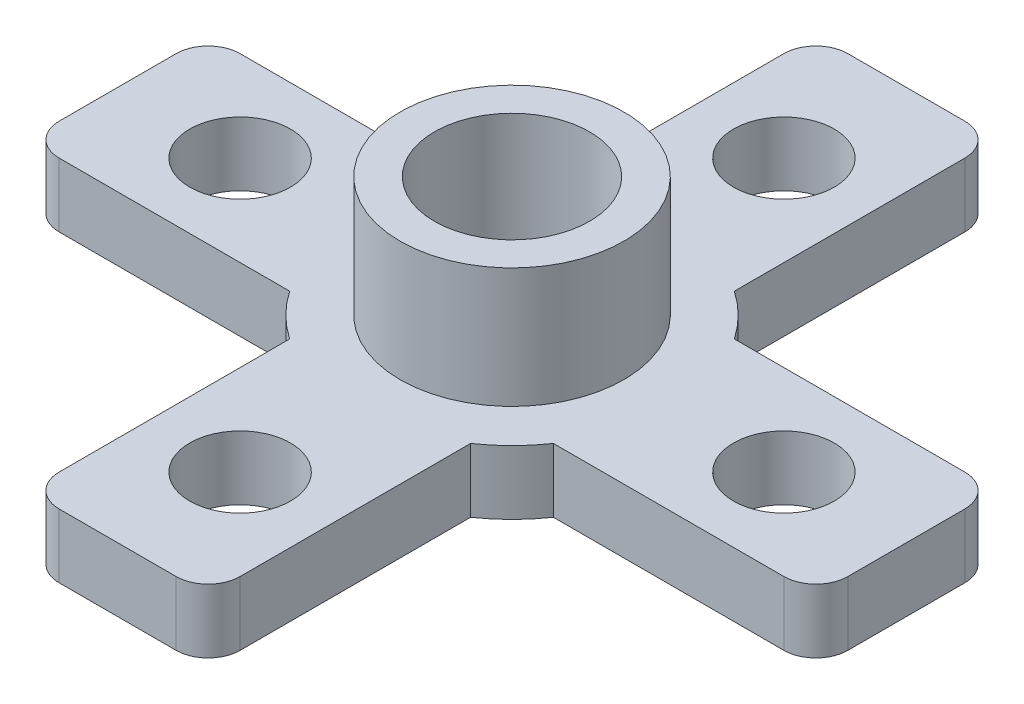
SolidWorks part; units mm, degrees
note: The reader was unsure of these and kept them because the rebuilt part matched: shared geometry of "Sketch1<3>", "Sketch1<4>".
ref_plane "Front Plane" through (0, 0, 0) normal (0, 0, 1) x (1, 0, 0)
ref_plane "Top Plane" through (0, 0, 0) normal (0, 1, 0) x (1, 0, 0)
ref_plane "Right Plane" through (0, 0, 0) normal (1, 0, 0) x (0, 0, -1)
sketch "Sketch1" plane through (0, 0, 0) normal (0, 1, 0) x (1, 0, 0)
  line L0 (2.8284, 2.8284) -> (12.3284, 2.8284)
  line L1 (-2.8284, 2.8284) -> (2.8284, -2.8284)
  line L2 (12.3284, 2.8284) -> (12.3284, -2.8284)
  line L3 (-2.8284, -2.8284) -> (2.8284, 2.8284)
  line L4 (-2.8284, 2.8284) -> (-2.8284, 12.3284)
  line L5 (-2.8284, 12.3284) -> (2.8284, 12.3284)
  line L6 (2.8284, 12.3284) -> (2.8284, 2.8284)
  line L7 (0, 0) -> (0, 8.5)
  line L8 (12.3284, -2.8284) -> (2.8284, -2.8284)
  line L9 (2.8284, -2.8284) -> (2.8284, -12.3284)
  line L10 (2.8284, -12.3284) -> (-2.8284, -12.3284)
  line L11 (-2.8284, -12.3284) -> (-2.8284, -2.8284)
  line L12 (-2.8284, -2.8284) -> (-12.3284, -2.8284)
  line L13 (-12.3284, -2.8284) -> (-12.3284, 2.8284)
  line L14 (-12.3284, 2.8284) -> (-2.8284, 2.8284)
  circle A0 centre (0, 0) radius 2.425
  circle A1 centre (0, 0) radius 4
  circle A2 centre (0, 8.5) radius 1.575
  circle A3 centre (8.5, 0) radius 1.575
  circle A4 centre (0, -8.5) radius 1.575
  circle A5 centre (-8.5, 0) radius 1.575
  circle A6 centre (0, 0) radius 3.5
  circle A7 centre (0, 0) radius 5
  circle A8 centre (0, 0) radius 1.125
  circle A9 centre (0, 0) radius 3
  point P33 (0, 0)
  dimension "D1" = 8
  dimension "D2" = 4.85
  dimension "D5" = 3.15
  dimension "D7" = 7
  dimension "D8" = 10
  dimension "D9" = 2.25
  dimension "D10" = 6
  dimension "D3" = 9.5
  dimension "D4" = 8.5
  dimension "D6" = 4
extrude "Boss-Extrude1" add sketch "Sketch1" along normal blind 2
extrude "Boss-Extrude2" add sketch "Sketch1<3>" along normal blind 5.75 contours L3 A6 L1 A0 | L1 A6 L3 A0 | L7 A6 L1 A0 | L3 A6 L7 A0 | L1 A6 L3 A0 | A9 L7 A6 L1 | A9 L3 A6 L7 | A9 L1 A6 L3 | A9 L3 A6 L1 | A9 L1 A6 L3
sketch "Sketch1<3>" plane through (0, 0, 0) normal (0, 1, 0) x (1, 0, 0) same geometry as "Sketch1"
fillet "Fillet1" radius 1 8 edges at (2.8284, 1, -12.3284) (12.3284, 1, -2.8284) (-2.8284, 1, -12.3284) (-12.3284, 1, -2.8284) (-12.3284, 1, 2.8284) (12.3284, 1, 2.8284) (2.8284, 1, 12.3284) (-2.8284, 1, 12.3284)
extrude "Cut-Extrude1" cut sketch "Sketch1<4>" along normal blind 1 contours L3 A9 L7 A0 | L1 A9 L3 A0 | A8 L1 A0 L3 | A8 L3 A0 L7 | A8 L7 A0 L1 | A8 L3 A0 L1 | A8 L1 A0 L3 | L1 A9 L3 A0 | L7 A9 L1 A0 | L3 A9 L1 A0
sketch "Sketch1<4>" plane through (0, 0, 0) normal (0, 1, 0) x (1, 0, 0) same geometry as "Sketch1"
